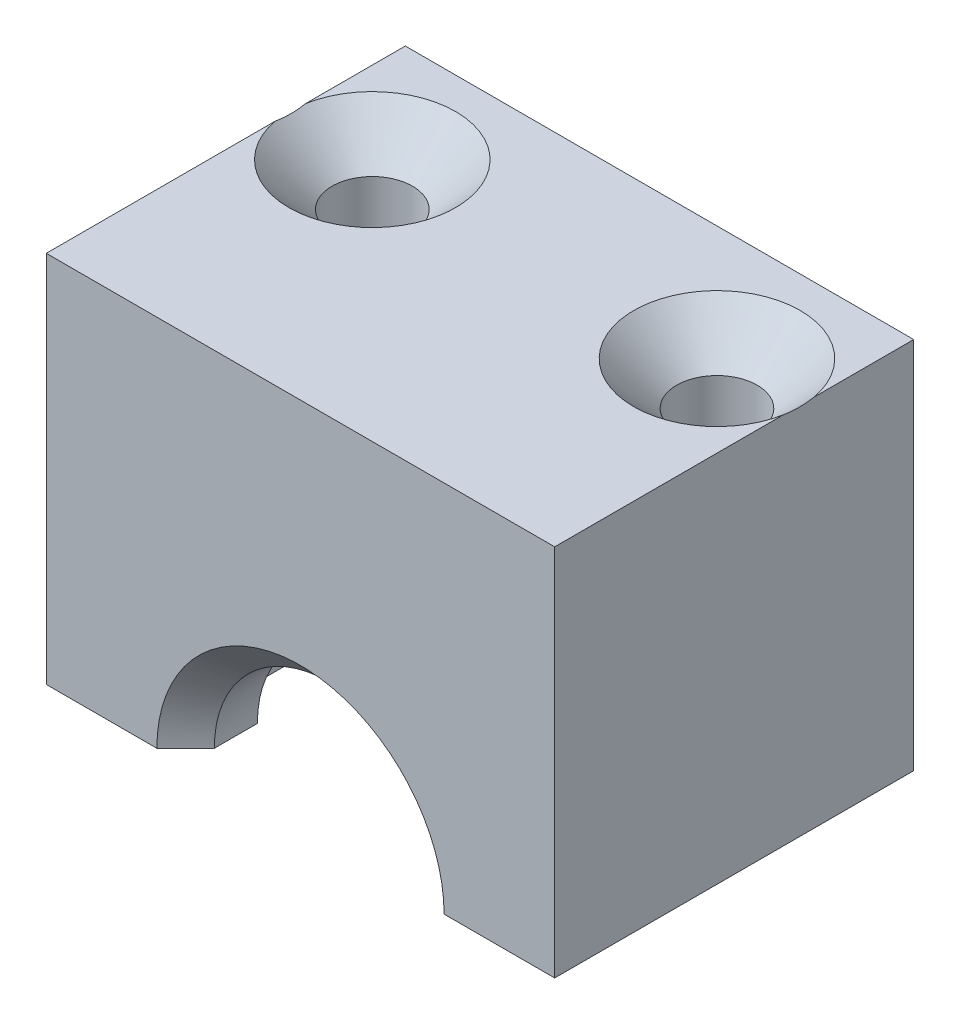
SolidWorks part; units mm, degrees
ref_plane "Спереди" through (0, 0, 0) normal (0, 0, 1) x (1, 0, 0)
ref_plane "Сверху" through (0, 0, 0) normal (0, 1, 0) x (1, 0, 0)
ref_plane "Справа" through (0, 0, 0) normal (1, 0, 0) x (0, 0, -1)
sketch "Эскиз2" plane through (0, 0, 0) normal (0, 0, 1) x (1, 0, 0)
  line L1 (-8.85, 0) -> (8.85, 0)
  line L2 (-8.85, 0) -> (-8.85, 13)
  line L3 (-8.85, 13) -> (8.85, 13)
  line L4 (8.85, 0) -> (8.85, 13)
  point P4 (0, 0)
  dimension "D1" = 17.7
  dimension "D2" = 13
extrude "тело" add sketch "Эскиз2" along normal mid plane 12.5
sketch "Эскиз3" plane through (0, 0, 6.25) normal (0, 0, 1) x (1, 0, 0)
  line L0 (-8.85, 0) -> (8.85, 0) construction
  circle A0 centre (0, 0) radius 4
  dimension "D1" = 8
extrude "вырез под гайки" cut sketch "Эскиз3" against normal through all
sketch "Эскиз4" plane through (0, 0, 6.25) normal (0, 0, 1) x (1, 0, 0)
  circle A0 centre (0, 0) radius 5.25
  dimension "D1" = 10.5
extrude "вырез под подшипник" cut sketch "Эскиз4" against normal blind 4.5 from offset 2.5 offset against normal yes
sketch "Эскиз5" plane through (0, 13, 0) normal (0, 1, 0) x (1, 0, 0)
  line L0 (-6, 2.25) -> (6, 2.25) construction
  line L1 (8.85, 6.25) -> (-8.85, 6.25) construction
  circle A0 centre (-6, 2.25) radius 1.4
  circle A1 centre (6, 2.25) radius 1.4
  point P4 (0, 0)
  point P8 (0, 2.25)
  dimension "D1" = 2.8
  dimension "D2" = 12
  dimension "D3" = 4
extrude "крепежные отверстия" cut sketch "Эскиз5" against normal through all
chamfer "Фаска2" distance 1 angle 45 2 edges at (0, 4, -6.25) (0, 4, 6.25)
chamfer "Фаска3" distance 1.5 angle 45 2 edges at (-6, 13, -0.85) (6, 13, -0.85)
